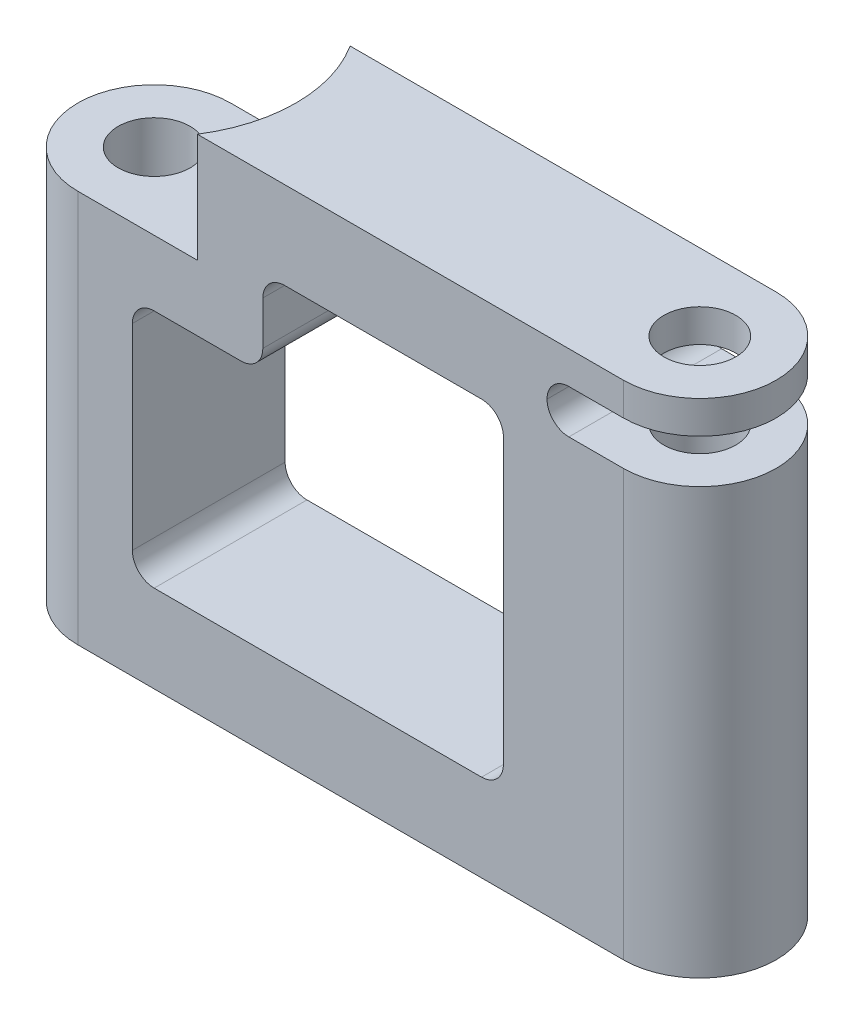
SolidWorks part; units mm, degrees
ref_plane "前视基准面" through (0, 0, 0) normal (0, 0, 1) x (1, 0, 0)
ref_plane "上视基准面" through (0, 0, 0) normal (0, 1, 0) x (1, 0, 0)
ref_plane "右视基准面" through (0, 0, 0) normal (1, 0, 0) x (0, 0, -1)
sketch "草图1" plane through (0, 0, 0) normal (0, 1, 0) x (1, 0, 0)
  line L0 (-12.5, 0) -> (12.5, 0) construction
  line L1 (-12.5, 3.5) -> (12.5, 3.5)
  line L2 (-12.5, -3.5) -> (12.5, -3.5)
  arc A0 (-12.5, 3.5) -> (-12.5, -3.5) centre (-12.5, 0) ccw
  arc A1 (12.5, -3.5) -> (12.5, 3.5) centre (12.5, 0) ccw
  point P2 (0, 0)
  dimension "D1" = 3.5
  dimension "D2" = 25
extrude "凸台-拉伸1" add sketch "草图1" along normal mid plane 23
sketch "草图2" plane through (0, 11.5, 0) normal (0, 1, 0) x (1, 0, 0)
  circle A0 centre (12.5, 0) radius 1.65
  circle A1 centre (-12.5, 0) radius 1.65
  dimension "D1" = 3.3
extrude "切除-拉伸1" cut sketch "草图2" against normal mid plane 93
sketch "草图4" plane through (0, 11.5, 0) normal (0, 1, 0) x (1, 0, 0)
  circle A0 centre (-12.5, 0) radius 6.5
  point P2 (-12.5, 0)
  dimension "D1" = 13
extrude "切除-拉伸2" cut sketch "草图4" against normal mid plane 10
sketch "草图5" plane through (0, 0, 3.5) normal (0, 0, 1) x (1, 0, 0)
  line L0 (9, 10) -> (16, 10)
  line L1 (16, -11.5) -> (16, 11.5) construction
  line L2 (16, 10) -> (16, 8)
  line L3 (16, 8) -> (9, 8)
  line L4 (9, 8) -> (9, 10)
  dimension "D1" = 2
  dimension "D2" = 7
  dimension "D3" = 1.5
extrude "切除-拉伸3" cut sketch "草图5" against normal mid plane 20
fillet "圆角1" radius 1 2 edges at (9, 8, 0) (9, 10, 0)
sketch "草图6" plane through (0, 0, 3.5) normal (0, 0, 1) x (1, 0, 0)
  line L0 (-10, 3.5) -> (-10, -7.5)
  line L1 (-10, -7.5) -> (7, -7.5)
  line L2 (7, -7.5) -> (7, 7.5)
  line L3 (7, 7.5) -> (-4.0228, 7.5)
  line L4 (-4.0228, 7.5) -> (-4.0228, 3.5)
  line L5 (-4.0228, 3.5) -> (-10, 3.5)
  line L6 (-7.0228, 11.5) -> (12.5, 11.5) construction
  line L7 (-12.5, -11.5) -> (12.5, -11.5) construction
  line L8 (-7.0228, 11.5) -> (-7.0228, 6.5) construction
  line L9 (-12.5, 6.5) -> (-7.0228, 6.5) construction
  line L10 (-12.5, 6.5) -> (-12.5, -11.5) construction
  arc A0 (9, 9) -> (10, 8) centre (10, 9) ccw construction
  dimension "D1" = 3
  dimension "D2" = 4
  dimension "D3" = 4
  dimension "D4" = 3
  dimension "D5" = 3
  dimension "D6" = 2.5
extrude "切除-拉伸4" cut sketch "草图6" against normal mid plane 50
fillet "圆角2" radius 1 6 edges at (-4.0228, 7.5, 0) (7, 7.5, 0) (7, -7.5, 0) (-10, -7.5, 0) (-10, 3.5, 0) (-4.0228, 3.5, 0)
